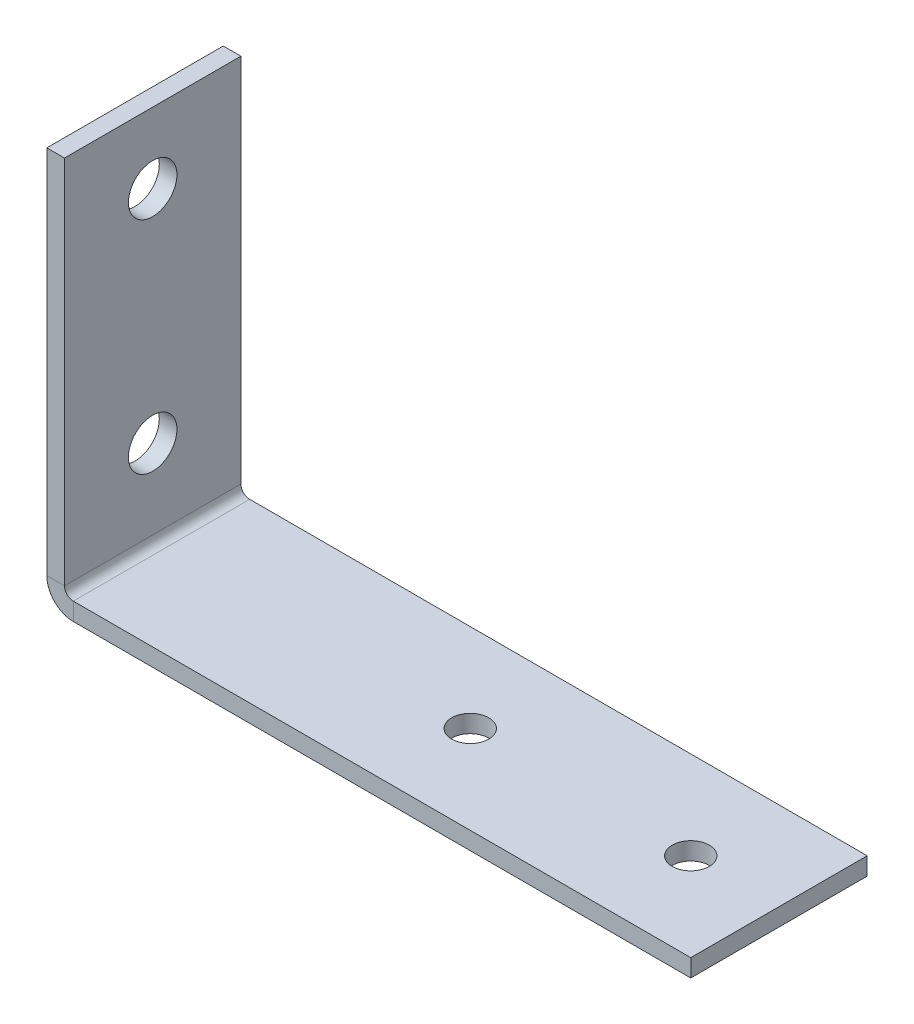
SolidWorks part; units mm, degrees
note: The reader was unsure of these and kept them because the rebuilt part matched: flange length of "边线-法兰1".
ref_plane "前视基准面" through (0, 0, 0) normal (0, 0, 1) x (1, 0, 0)
ref_plane "上视基准面" through (0, 0, 0) normal (0, 1, 0) x (1, 0, 0)
ref_plane "右视基准面" through (0, 0, 0) normal (1, 0, 0) x (0, 0, -1)
sketch "草图1" plane through (0, 0, 0) normal (0, 1, 0) x (1, 0, 0)
  line L1 (-35, 20) -> (35, 20)
  line L2 (-35, 20) -> (-35, 0)
  line L3 (-35, 0) -> (35, 0)
  line L4 (35, 20) -> (35, 0)
  point P5 (0, 0)
  dimension "D1" = 70
  dimension "D2" = 20
  dimension "D3" = 0
  dimension "D4" = 0
base flange "基体-法兰1" sketch "草图1" thickness 2 reverse thickness direction no parameters "D1"=1
edge flange "边线-法兰1" sketch "草图14" flange angle 90 flange length 45 flange position bend outside bend radius 1 thickness 2 relief rectangular parameters "D6"=10
bend "边线折弯1" bend radius 1 bend angle 90 parameters "D5"=1
sketch "草图14" plane through (-35, 0, 0) normal (-1, 0, 0) x (0, 0, 1)
  line L0 (-20, 0) -> (0, 0) construction
  line L1 (-20, 0) -> (0, 0)
  line L2 (-20, 0) -> (-20, 43)
  line L3 (-20, 43) -> (0, 43)
  line L4 (0, 43) -> (0, 0)
hole_wizard "大小mm 暗销孔1" positions "3D草图1" profile "草图15" hole size "Ø8.0" standard "GB"
sketch3d "3D草图1"
  line L0 (-36, 1, 0) -> (-36, 43, 0) construction
  line L1 (-36, 43, 0) -> (-36, 43, -20) construction
  point P0 (-36, 35, -10)
  point P2 (-36, 10, -10)
  dimension "D1" = 25
  dimension "D2" = 10
  dimension "D3" = 10
  dimension "D4" = 8
sketch "草图15" plane through (-36, 35, -10) normal (0, 1, 0) x (0, 0, -1)
  line L0 (0, 0) -> (0, 9.6524)
  line L1 (0, 9.6524) -> (2.75, 8)
  line L2 (2.75, 8) -> (2.75, 0)
  line L5 (2.75, 0) -> (0, 0)
  line L10 (0, 9.6524) -> (-2.75, 8) construction
  line L11 (0, -6.35) -> (0, 107.95) construction
  dimension "孔直径" = 5.5
  dimension "孔深度" = 8
  dimension "导头角度" = 118
hole_wizard "M5 螺纹孔1" positions "3D草图2" profile "草图16" tap size "M5" standard "GB"
sketch3d "3D草图2"
  line L0 (-35, 0, 0) -> (35, 0, 0) construction
  line L1 (35, 0, 0) -> (35, 0, -20) construction
  point P0 (0, 0, -10)
  point P2 (25, 0, -10)
  point P12 (33.535, 0, -37.106)
  dimension "D1" = 10
  dimension "D2" = 10
  dimension "D3" = 25
  dimension "D4" = 10
sketch "草图16" plane through (0, 0, -10) normal (1, 0, 0) x (0, 0, 1)
  line L0 (0, 0) -> (0, 13.6618)
  line L1 (0, 13.6618) -> (2.1, 12.4)
  line L2 (2.1, 12.4) -> (2.1, 0)
  line L5 (2.1, 0) -> (0, 0)
  line L10 (0, 13.6618) -> (-2.1, 12.4) construction
  line L11 (0, -6.35) -> (0, 107.95) construction
  dimension "螺纹孔钻头直径" = 4.2
  dimension "螺纹孔钻头深度" = 12.4
  dimension "导头角度" = 118
cosmetic thread "孔螺蚊线1"
cosmetic thread "孔螺蚊线3"
sketch "折弯-线1" plane through (0, 0, 0) normal (0, 1, 0) x (1, 0, 0)
sketch "边界框1" plane through (0, 0, 0) normal (0, 1, 0) x (1, 0, 0)
sheet metal parameters "钣金6" thickness 2 parameters "D1"=1
flat pattern "平板型式6" [suppressed]
sketch "折弯-线2" plane through (0, 0, 0) normal (0, 1, 0) x (1, 0, 0)
sketch "边界框2" [suppressed] plane through (0, 0, 0) normal (0, 1, 0) x (1, 0, 0)
sheet metal parameters "钣金7" thickness 2 parameters "D1"=1
flat pattern "平板型式6" [suppressed]
sketch "折弯-线2" plane through (0, 0, 0) normal (0, 1, 0) x (1, 0, 0)
sketch "边界框2" [suppressed] plane through (0, 0, 0) normal (0, 1, 0) x (1, 0, 0)
bend of the flat pattern "展平-<边线折弯1>1"
sheet metal parameters "钣金10" thickness 2 parameters "D1"=1
flat pattern "平板型式6" [suppressed]
sketch "折弯-线2" plane through (0, 0, 0) normal (0, 1, 0) x (1, 0, 0)
sketch "边界框2" [suppressed] plane through (0, 0, 0) normal (0, 1, 0) x (1, 0, 0)
bend of the flat pattern "展平-<边线折弯1>1"
sheet metal parameters "钣金11" thickness 2 parameters "D1"=1
flat pattern "平板型式6" [suppressed]
sketch "折弯-线2" plane through (0, 0, 0) normal (0, 1, 0) x (1, 0, 0)
sketch "边界框2" [suppressed] plane through (0, 0, 0) normal (0, 1, 0) x (1, 0, 0)
bend of the flat pattern "展平-<边线折弯1>1"
